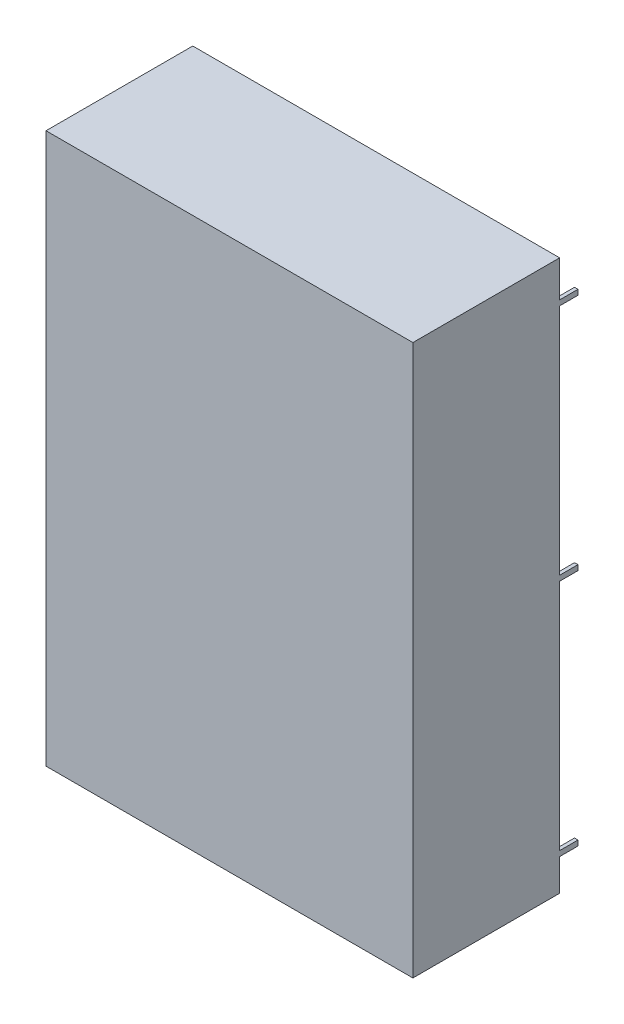
SolidWorks part; units mm, degrees
ref_plane "Plan de face" through (0, 0, 0) normal (0, 0, 1) x (1, 0, 0)
ref_plane "Plan de dessus" through (0, 0, 0) normal (0, 1, 0) x (1, 0, 0)
ref_plane "Plan de droite" through (0, 0, 0) normal (1, 0, 0) x (0, 0, -1)
sketch "Esquisse1" plane through (0, 0, 0) normal (0, 0, 1) x (1, 0, 0)
  line L1 (-56.626, 31.2883) -> (143.374, 31.2883)
  line L2 (-56.626, 31.2883) -> (-56.626, -268.7117)
  line L3 (-56.626, -268.7117) -> (143.374, -268.7117)
  line L4 (143.374, 31.2883) -> (143.374, -268.7117)
  dimension "D1" = 200
  dimension "D2" = 300
extrude "Boss.-Extru.1" add sketch "Esquisse1" along normal blind 80
shell "Coque1" thickness 4 removed face at (43.374, -118.7117, 0)
sketch "Esquisse3" plane through (0, 0, 0) normal (0, 0, -1) x (-1, 0, 0)
  line L8 (54.726, -266.8117) -> (54.726, 29.3883)
  line L9 (54.726, 29.3883) -> (-141.474, 29.3883)
  line L10 (-141.474, 29.3883) -> (-141.474, -266.8117)
  line L11 (-141.474, -266.8117) -> (54.726, -266.8117)
  line L12 (54.726, -266.8117) -> (54.726, 29.3883)
  line L13 (54.726, 29.3883) -> (-141.474, 29.3883)
  line L14 (-141.474, 29.3883) -> (-141.474, -266.8117)
  line L15 (-141.474, -266.8117) -> (54.726, -266.8117)
  dimension "D1" = 1.9
extrude "Enlèv. mat.-Extru.2" cut sketch "Esquisse3" against normal blind 4.1
sketch "Esquisse4" plane through (0, 0, 76) normal (0, 0, -1) x (-1, 0, 0)
  line L0 (15.126, -185.7117) -> (52.626, -185.7117)
  line L1 (52.626, 27.2883) -> (52.626, -264.7117) construction
  line L2 (15.126, -185.7117) -> (15.126, -264.7117)
  line L3 (52.626, -264.7117) -> (-139.374, -264.7117) construction
  line L4 (-101.874, -185.7117) -> (-139.374, -185.7117)
  line L5 (-101.874, -185.7117) -> (-101.874, -264.7117)
  line L6 (-139.374, -264.7117) -> (-139.374, 27.2883) construction
  line L8 (-101.874, -51.7117) -> (-139.374, -51.7117)
  line L9 (-101.874, -51.7117) -> (-101.874, 27.2883)
  line L10 (-139.374, 27.2883) -> (52.626, 27.2883) construction
  line L11 (15.126, -51.7117) -> (52.626, -51.7117)
  line L12 (15.126, -51.7117) -> (15.126, 27.2883)
  line L13 (-119.374, 7.2883) -> (-119.374, 27.2883)
  line L14 (-119.374, 27.2883) -> (-119.374, 7.2883)
  line L15 (-119.374, 7.2883) -> (-139.374, 7.2883)
  circle A0 centre (15.126, -185.7117) radius 9
  circle A1 centre (-101.874, -185.7117) radius 9
  circle A2 centre (15.126, -51.7117) radius 9
  circle A3 centre (-101.874, -51.7117) radius 9
  circle A4 centre (-119.374, 7.2883) radius 9
  dimension "D1" = 37.5
  dimension "D2" = 79
  dimension "D3" = 37.5
  dimension "D4" = 79
  dimension "D5" = 79
  dimension "D6" = 79
  dimension "D7" = 37.5
  dimension "D8" = 37.5
  dimension "D9" = 20
  dimension "D10" = 20
extrude "Boss.-Extru.2" add sketch "Esquisse4" along normal blind 67.9 contours A4
sketch "Esquisse5" plane through (0, 0, 8.1) normal (0, 0, -1) x (-1, 0, 0)
  circle A3 centre (-119.374, 7.2883) radius 2.5
  circle A4 centre (-119.374, 7.2883) radius 2.5
  dimension "D1" = 6.5
extrude "Enlèv. mat.-Extru.3" cut sketch "Esquisse5" against normal blind 30
extrude "Boss.-Extru.3" add sketch "Esquisse4<4>" along normal blind 15 contours L9 A3 L8 | L8 A3 L9 | L2 A0 L0 | L0 A0 L2 | A2 | A1 region at (-13.8528, -184.4384, 76) region at (-18.9458, -189.5314, 76) region at (100.6007, -52.9849, 76) region at (105.6937, -47.8919, 76)
sketch "Esquisse4<4>" plane through (0, 0, 76) normal (0, 0, -1) x (-1, 0, 0) same geometry as "Esquisse4"
sketch "Esquisse6" plane through (0, 0, 61) normal (0, 0, -1) x (-1, 0, 0)
  circle A3 centre (-101.874, -51.7117) radius 2.5
  circle A4 centre (-101.874, -51.7117) radius 2.5
  circle A6 centre (15.126, -51.7117) radius 2.5
  circle A7 centre (15.126, -51.7117) radius 2.5
  circle A9 centre (-101.874, -185.7117) radius 2.5
  circle A10 centre (-101.874, -185.7117) radius 2.5
  circle A12 centre (15.126, -185.7117) radius 2.5
  circle A13 centre (15.126, -185.7117) radius 2.5
  dimension "D1" = 6.5
  dimension "D2" = 6.5
  dimension "D3" = 6.5
  dimension "D4" = 6.5
extrude "Enlèv. mat.-Extru.6" cut sketch "Esquisse6" against normal blind 10
sketch "Esquisse8" plane through (0, 0, 76) normal (0, 0, -1) x (-1, 0, 0)
  line L0 (32.626, 7.2883) -> (52.626, 7.2883)
  line L1 (52.626, 27.2883) -> (52.626, -264.7117) construction
  line L2 (32.626, 7.2883) -> (32.626, 27.2883)
  line L3 (-139.374, 27.2883) -> (52.626, 27.2883) construction
  line L4 (32.626, -244.7117) -> (52.626, -244.7117)
  line L5 (32.626, -244.7117) -> (32.626, -264.7117)
  line L6 (52.626, -264.7117) -> (-139.374, -264.7117) construction
  line L7 (-119.374, -244.7117) -> (-139.374, -244.7117)
  line L8 (-139.374, -264.7117) -> (-139.374, 27.2883) construction
  line L9 (-119.374, -244.7117) -> (-119.374, -264.7117)
  circle A0 centre (32.626, 7.2883) radius 9
  circle A1 centre (32.626, -244.7117) radius 9
  circle A2 centre (-119.374, -244.7117) radius 9
  dimension "D1" = 20
  dimension "D2" = 20
  dimension "D3" = 20
  dimension "D4" = 20
  dimension "D5" = 20
  dimension "D6" = 20
extrude "Boss.-Extru.5" add sketch "Esquisse8" along normal blind 68 contours L0 A0 L2 | L2 A0 L0 | L5 A1 L4 | L4 A1 L5 | A2 region at (-36.4458, 11.1081, 76) region at (-31.3528, 6.0151, 76) region at (-31.3528, -243.4384, 76) region at (-36.4458, -248.5314, 76)
sketch "Esquisse9" plane through (0, 0, 8) normal (0, 0, -1) x (-1, 0, 0)
  circle A2 centre (32.626, 7.2883) radius 2.5
  circle A3 centre (32.626, 7.2883) radius 2.5
  circle A4 centre (32.626, -244.7117) radius 2.5
  circle A5 centre (32.626, -244.7117) radius 2.5
  circle A7 centre (-119.374, -244.7117) radius 2.5
  circle A8 centre (-119.374, -244.7117) radius 2.5
  dimension "D1" = 6.5
  dimension "D2" = 6.5
  dimension "D3" = 6.5
extrude "Enlèv. mat.-Extru.8" cut sketch "Esquisse9" against normal blind 30 contours A8 | A5 | A3
sketch "Esquisse10" plane through (0, 0, 0) normal (0, 0, -1) x (-1, 0, 0)
  line L0 (-141.474, 29.3883) -> (-141.474, -266.8117) construction
  line L1 (-141.474, -251.4034) -> (-143.374, -251.4034)
  line L2 (-141.474, -251.4034) -> (-141.474, -248.5629)
  line L3 (-141.474, -248.5629) -> (-143.374, -248.5629)
  line L4 (-143.374, -251.4034) -> (-143.374, -248.5629)
  line L5 (-143.374, -268.7117) -> (-143.374, 31.2883) construction
extrude "Boss.-Extru.6" add sketch "Esquisse10" along normal blind 10
pattern_linear "Répétition linéaire1" count 2 spacing 198.1 along (-1, 0, 0) of "Boss.-Extru.6"
pattern_linear "Répétition linéaire2" count 3 spacing 130 along (0, 1, 0) of "Répétition linéaire1"
